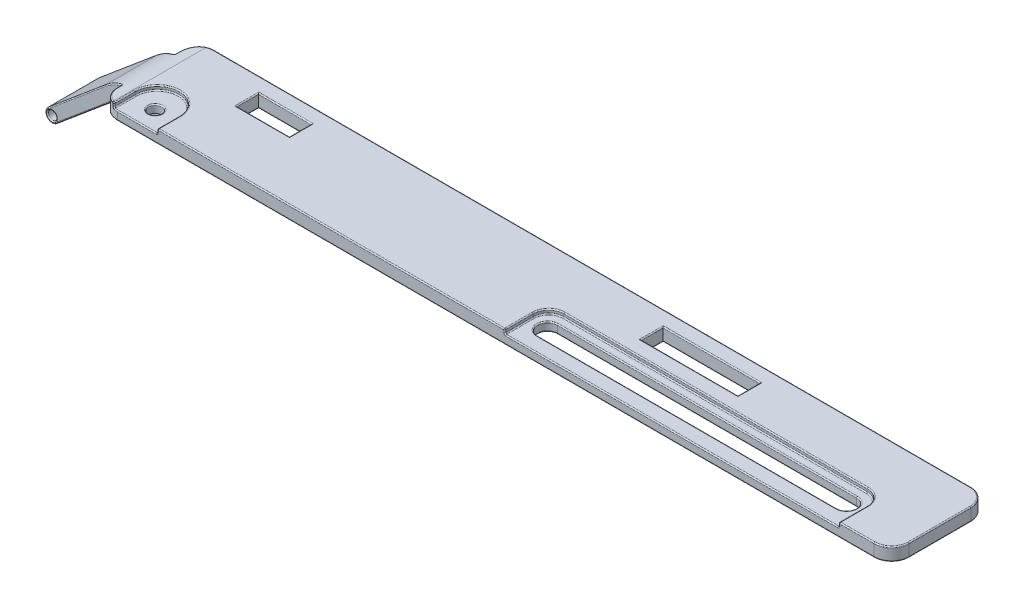
SolidWorks part; units mm, degrees
ref_plane "Front Plane" through (0, 0, 0) normal (0, 0, 1) x (1, 0, 0)
ref_plane "Top Plane" through (0, 0, 0) normal (0, 1, 0) x (1, 0, 0)
ref_plane "Right Plane" through (0, 0, 0) normal (1, 0, 0) x (0, 0, -1)
sketch "Sketch1" plane through (0, 0, 0) normal (0, 0, 1) x (1, 0, 0)
  line L0 (-182.7882, -2.3396) -> (-195, -12.5865)
  line L1 (0, 0) -> (-176.3603, 0)
  line L2 (0, 0) -> (0, 3)
  line L3 (0, 3) -> (-177.4522, 3)
  line L6 (-196.9284, -10.2884) -> (-183.8801, 0.6604)
  arc A0 (-196.9284, -10.2884) -> (-195, -12.5865) centre (-195.9642, -11.4374) ccw
  circle A1 centre (-195.9642, -11.4374) radius 1
  arc A2 (-176.3603, 0) -> (-182.7882, -2.3396) centre (-176.3603, -10) ccw
  arc A3 (-177.4522, 3) -> (-183.8801, 0.6604) centre (-177.4522, -7) ccw
  point P11 (-180, 0)
  dimension "D1" = 2
  dimension "D2" = 10
  dimension "D6" = 10
  dimension "D3" = 140
  dimension "D4" = 15
  dimension "D5" = 3
extrude "Boss-Extrude1" add sketch "Sketch1" along normal blind 11 and the other way blind 11
sketch "Sketch2" plane through (0, 0, 11) normal (0, 0, 1) x (1, 0, 0)
  line L0 (0, 0) -> (0, 3) construction
  line L1 (-210.1499, 9.6657) -> (-180, 9.6657)
  line L2 (-210.1499, 9.6657) -> (-210.1499, -17.5852)
  line L3 (-210.1499, -17.5852) -> (-180, -17.5852)
  line L4 (-180, 9.6657) -> (-180, -17.5852)
  dimension "D1" = 180
extrude "Cut-Extrude1" cut sketch "Sketch2" against normal blind 5
sketch "Sketch3" plane through (0, 0, -11) normal (0, 0, -1) x (-1, 0, 0)
  line L0 (0, 0) -> (0, 3) construction
  line L1 (180, 28.7292) -> (251.8205, 28.7292)
  line L2 (180, 28.7292) -> (180, -54.8714)
  line L3 (180, -54.8714) -> (251.8205, -54.8714)
  line L4 (251.8205, 28.7292) -> (251.8205, -54.8714)
  dimension "D1" = 180
extrude "Cut-Extrude2" cut sketch "Sketch3" against normal blind 5
sketch "Sketch4" plane through (0, 3, 0) normal (0, 1, 0) x (1, 0, 0)
  line L10 (-175.2939, 0) -> (-12.4374, 0) construction
  line L11 (0, 0) -> (-176.3603, 0) construction
  line L12 (-70.4522, 7.5) -> (-48.4522, 7.5)
  line L13 (-48.4522, 2.5) -> (-48.4522, 7.5)
  line L14 (-70.4522, 2.5) -> (-48.4522, 2.5)
  line L15 (-70.4522, 2.5) -> (-70.4522, 7.5)
  line L16 (-162.4522, 7.5) -> (-150.4522, 7.5)
  line L17 (-150.4522, 2.5) -> (-150.4522, 7.5)
  line L18 (-162.4522, 2.5) -> (-150.4522, 2.5)
  line L19 (-162.4522, 2.5) -> (-162.4522, 7.5)
extrude "Cut-Extrude3" cut sketch "Sketch4" against normal up to next
sketch "Sketch5" plane through (0, 3, 0) normal (0, 1, 0) x (1, 0, 0)
  line L14 (-177.4522, 0) -> (0, 0) construction
  line L15 (-177.4522, 11) -> (-177.4522, -11) construction
  line L16 (-84.5, -1) -> (-15.5, -1)
  line L17 (-12, -11) -> (-12, -4.5)
  line L18 (-88, -11) -> (-12, -11)
  line L19 (-88, -11) -> (-88, -4.5)
  line L20 (-177, -6) -> (-177, -11)
  line L21 (-177, -11) -> (-167, -11)
  line L22 (-167, -11) -> (-167, -6)
  arc A3 (-15.5, -1) -> (-12, -4.5) centre (-15.5, -4.5) cw
  arc A4 (-84.5, -1) -> (-88, -4.5) centre (-84.5, -4.5) ccw
  arc A5 (-177, -6) -> (-167, -6) centre (-172, -6) cw
  point P14 (-12, 1)
  point P17 (-88, 1)
  dimension "D1" = 76
extrude "Cut-Extrude4" cut sketch "Sketch5" against normal blind 1
sketch "Sketch6" plane through (0, 3, 0) normal (0, 1, 0) x (1, 0, 0)
  line L0 (0, 0) -> (-177.4522, 0) construction
  line L5 (-177.4522, 11) -> (-177.4522, -11) construction
  line L9 (-84, -3) -> (-16, -3)
  line L10 (-84, -7.5) -> (-16, -7.5)
  arc A4 (-84, -7.5) -> (-84, -3) centre (-84, -5.25) cw
  arc A5 (-16, -3) -> (-16, -7.5) centre (-16, -5.25) cw
  circle A6 centre (-172, -6.5) radius 1.5
extrude "Cut-Extrude5" cut sketch "Sketch6" against normal up to next
fillet "Fillet1" radius 4 4 edges at (-180, 0.992, 11) (-180, 0.992, -11) (0, 1.5, 11) (0, 1.5, -11)
fillet "Fillet2" radius 0.25 86 edges at (-180, -0.6859, 6.5) (-178.6841, -0.2738, 9.9657) (-180, -0.6859, -6.5) (-179.1965, -0.4106, -9.4047) (-180, 2.67, -6.5) (-179.4342, 2.8016, -9.0509) (-180, 2.67, 6.5) (-179.1546, 2.854, 9.4593) (-196.9642, -11.4374, -6) (-181.4615, -1.399, -6) (-180, 0.992, -6) (-182.0511, 1.8797, -6) (-190.4042, -4.814, -6) (-197.1132, -12.4016, -6) (-188.8941, -7.463, -6) (-194.9642, -11.4374, 6) (-181.4615, -1.399, 6) (-188.8941, -7.463, 6) (-197.1132, -12.4016, 6) (-190.4042, -4.814, 6) (-182.0511, 1.8797, 6) (-180, 0.992, 6) (-1.1716, 0, 9.8284) (0, 0, 0) (-1.1716, 0, -9.8284) (-90, 0, -11) (-176.1803, 0, -10.9959) (-176.1803, 0, 10.9959) (-90, 0, 11) (-176.7388, 3, -10.9312) (-90, 3, -11) (-1.1716, 3, -9.8284) (0, 3, 0) (-1.1716, 3, 9.8284) (-8, 3, 11) (-177.2283, 3, 10.8068) (-48.4522, 0, -5) (-59.4522, 0, -2.5) (-70.4522, 0, -5) (-156.4522, 0, -7.5) (-150.4522, 0, -5) (-156.4522, 0, -2.5) (-162.4522, 0, -5) (-156.4522, 3, -2.5) (-150.4522, 3, -5) (-156.4522, 3, -7.5) (-162.4522, 3, -5) (-12, 3, 7.75) (-13.0251, 3, 2.0251) (-50, 3, 1) (-86.9749, 3, 2.0251) (-88, 3, 7.75) (-127.5, 3, 11) (-167, 3, 8.5) (-172, 3, 1) (-177, 3, 8.4365) (-59.4522, 3, -7.5) (-70.4522, 3, -5) (-59.4522, 3, -2.5) (-48.4522, 3, -5) (-59.4522, 0, -7.5) (-172, 0, 5) (-50, 0, 3) (-13.75, 0, 5.25) (-50, 0, 7.5) (-86.25, 0, 5.25) (-12, 2.5, 11) (-88, 2.5, 11) (-167, 2.5, 11) (-177, 2.5, 10.873) (-50, 2, 1) (-13.0251, 2, 2.0251) (-12, 2, 7.75) (-50, 2, 11) (-88, 2, 7.75) (-86.9749, 2, 2.0251) (-50, 2, 7.5) (-13.75, 2, 5.25) (-50, 2, 3) (-86.25, 2, 5.25) (-172, 2, 1) (-167, 2, 8.5) (-171.5, 2, 11) (-176.504, 2, 10.9681) (-177, 2, 8.4365) (-170.5, 2, 6.5)
